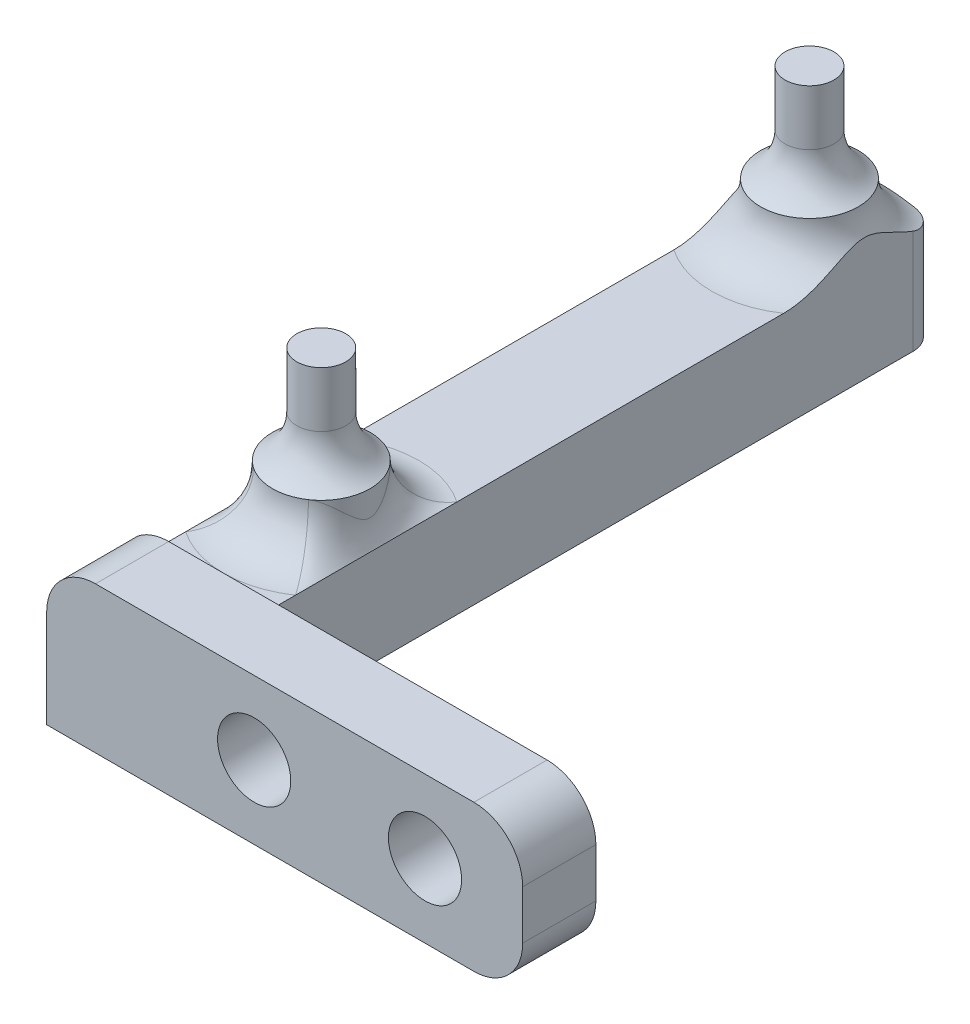
SolidWorks part; units mm, degrees
ref_plane "Front Plane" through (0, 0, 0) normal (0, 0, 1) x (1, 0, 0)
ref_plane "Top Plane" through (0, 0, 0) normal (0, 1, 0) x (1, 0, 0)
ref_plane "Right Plane" through (0, 0, 0) normal (1, 0, 0) x (0, 0, -1)
sketch "Sketch1" plane through (0, 0, 0) normal (0, 1, 0) x (1, 0, 0)
  line L0 (0, 0) -> (0, 15.9628) construction
  line L2 (-2.25, 17.3926) -> (2.25, 17.3926)
  line L3 (-2.25, 17.3926) -> (-2.25, -8.6074)
  line L4 (-2.25, -8.6074) -> (2.25, -8.6074)
  line L5 (2.25, 17.3926) -> (2.25, -8.6074)
  line L6 (-2.25, -8.6074) -> (2.25, -8.6074)
  line L7 (-2.25, -8.6074) -> (-2.25, -14.6074)
  line L8 (-2.25, -14.6074) -> (2.25, -14.6074)
  line L9 (2.25, -8.6074) -> (2.25, -14.6074)
  circle A0 centre (0, 14.3926) radius 2
  circle A1 centre (0, -5.6074) radius 2
  dimension "D1" = 2.25
  dimension "D3" = 4
  dimension "D4" = 4
  dimension "D5" = 3
  dimension "D6" = 3
  dimension "D7" = 20
  dimension "D2" = 4.5
  dimension "D8" = 6
extrude "Boss-Extrude1" add sketch "Sketch1" along normal blind 4 contours L9 L4 L7 L8 | A0 L2 L3 L4 L5 A1 region at (0, 0, -4.3926) region at (0, 0, 11.6074)
extrude "Boss-Extrude2" add sketch "Sketch1<3>" along normal blind 6 contours A1 | A0 L0 | L0 A0 region at (1.3742, 0, -13.0184) region at (0, 0, 5.6074)
sketch "Sketch1<3>" plane through (0, 0, 0) normal (0, 1, 0) x (1, 0, 0) same geometry as "Sketch1"
sketch "Sketch2" plane through (0, 6, 0) normal (0, 1, 0) x (1, 0, 0)
  circle A0 centre (0, 14.3926) radius 1
  circle A1 centre (0, -5.6074) radius 1
  dimension "D1" = 2
  dimension "D2" = 2
extrude "Boss-Extrude3" add sketch "Sketch2" along normal blind 4
fillet "Fillet1" radius 2 1 edges at (0, 6, 6.6074)
fillet "Fillet2" radius 2 1 edges at (0, 6, -13.3926)
fillet "Fillet3" radius 2 1 edges at (0, 4, 7.6074)
fillet "Fillet4" radius 2 1 edges at (0, 4, -12.3926)
sketch "Sketch3" plane through (2.25, 0, 0) normal (1, 0, 0) x (0, 0, -1)
  line L0 (17.3926, 0) -> (-14.6074, 0) construction
  line L1 (-14.6074, 4) -> (-11.6074, 4)
  line L2 (-14.6074, 4) -> (-14.6074, 0)
  line L3 (-14.6074, 0) -> (-11.6074, 0)
  line L4 (-11.6074, 4) -> (-11.6074, 0)
  dimension "D1" = 3
extrude "Boss-Extrude4" add sketch "Sketch3" along normal blind 15
sketch "Sketch5" plane through (0, 4, 0) normal (0, 1, 0) x (1, 0, 0)
  line L0 (-2.25, -14.6074) -> (17.25, -14.6074) construction
  line L1 (-2.25, -14.6074) -> (2.25, -14.6074)
  line L2 (-2.25, -14.6074) -> (-2.25, -11.6074)
  line L3 (-2.25, -11.6074) -> (2.25, -11.6074)
  line L4 (2.25, -14.6074) -> (2.25, -11.6074)
extrude "Boss-Extrude5" add sketch "Sketch5" along normal blind 2
sketch "Sketch7" plane through (2.25, 0, 0) normal (1, 0, 0) x (0, 0, -1)
  line L1 (-11.6074, 6) -> (-14.6074, 6)
  line L2 (-11.6074, 6) -> (-11.6074, 4)
  line L3 (-11.6074, 4) -> (-14.6074, 4)
  line L4 (-14.6074, 6) -> (-14.6074, 4)
extrude "Boss-Extrude6" add sketch "Sketch7" along normal up to surface (15 mm away) up to face at (17.25, 2, 13.1074)
sketch "Sketch8" plane through (0, 0, 11.6074) normal (0, 0, -1) x (-1, 0, 0)
  line L0 (-17.25, 3) -> (4.7513, 3) construction
  line L1 (-17.25, 0) -> (-17.25, 6) construction
  line L2 (-2.25, 0) -> (-2.25, 4) construction
  circle A0 centre (-6.25, 3) radius 1.5
  circle A1 centre (-13.25, 3) radius 1.5
  dimension "D1" = 3
  dimension "D2" = 3
  dimension "D3" = 4
  dimension "D4" = 4
extrude "Cut-Extrude1" cut sketch "Sketch8" against normal through all
fillet "Fillet12" radius 2 2 edges at (2.25, 2, 11.6074) (0, 4, 11.6074)
fillet "Fillet13" radius 2 1 edges at (-2.25, 6, 13.1074)
fillet "Fillet14" radius 2 2 edges at (17.25, 6, 13.1074) (17.25, 0, 13.1074)
fillet "Fillet16" radius 1 2 edges at (-2.25, 2.0078, -17.3926) (2.25, 2.0078, -17.3926)
